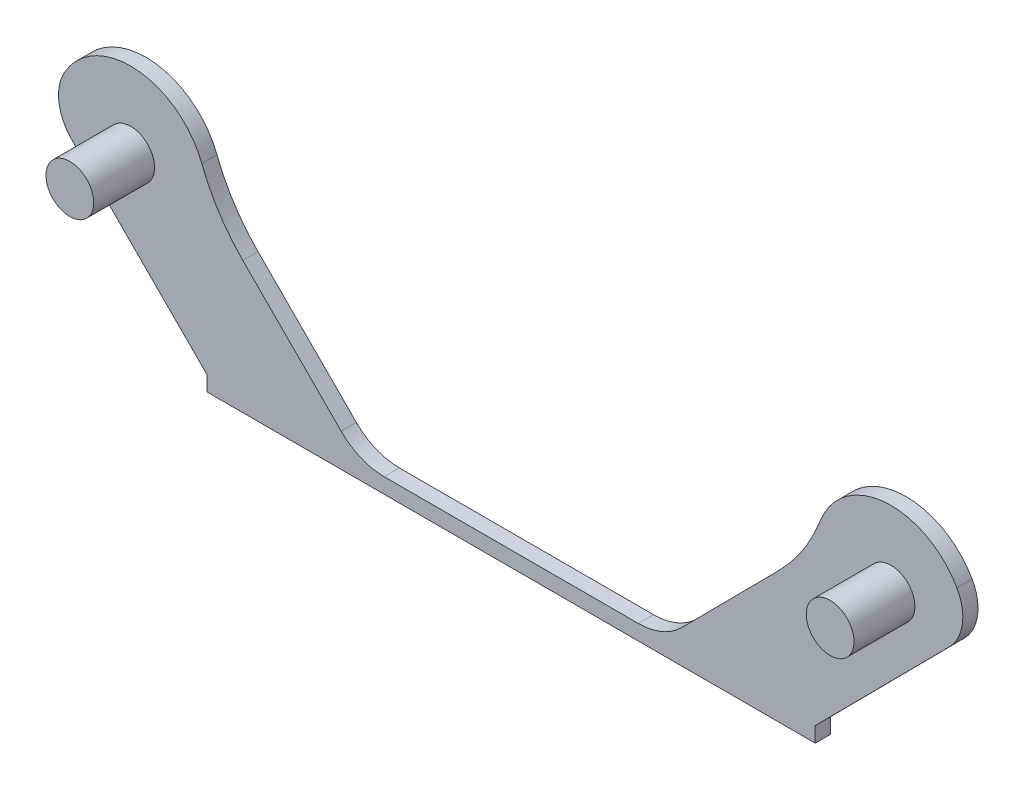
SolidWorks part; units mm, degrees
material "1060 Alloy"
ref_plane "Front Plane" through (0, 0, 0) normal (0, 0, 1) x (1, 0, 0)
ref_plane "Top Plane" through (0, 0, 0) normal (0, 1, 0) x (1, 0, 0)
ref_plane "Right Plane" through (0, 0, 0) normal (1, 0, 0) x (0, 0, -1)
sketch "Sketch1" plane through (0, 0, 0) normal (0, 0, 1) x (1, 0, 0)
  line L5 (50.8, 0) -> (-50.8, 0)
  line L6 (-50.8, 2.54) -> (-50.8, 0)
  line L8 (-50.8, 2.54) -> (-73.3412, 25.1777)
  line L16 (50.8, 2.54) -> (50.8, 0)
  line L17 (-44.7815, 22.0182) -> (-28.3648, 5.5312)
  line L19 (44.8202, 22.0295) -> (28.4837, 5.5477)
  line L20 (21.2678, 2.54) -> (-21.1652, 2.54)
  line L21 (73.2365, 25.1762) -> (50.8, 2.54)
  arc A0 (-74.5846, 34.2871) -> (-51.6423, 32.612) centre (-63.5068, 28.0625) cw
  arc A1 (74.4553, 34.2951) -> (51.6365, 32.586) centre (63.4487, 28.0625) ccw
  circle A2 centre (-63.5068, 28.0625) radius 3.9878
  circle A3 centre (63.4487, 28.0625) radius 3.9878
  arc A4 (-73.3412, 25.1777) -> (-74.5846, 34.2871) centre (-67.9415, 30.5544) cw
  arc A5 (44.8202, 22.0295) -> (51.6365, 32.586) centre (23.1723, 43.4864) ccw
  arc A6 (-44.7815, 22.0182) -> (-51.6423, 32.612) centre (-23.1829, 43.5247) cw
  arc A7 (74.4553, 34.2951) -> (73.2365, 25.1762) centre (67.8246, 30.5404) cw
  arc A8 (21.2678, 2.54) -> (28.4837, 5.5477) centre (21.2678, 12.7) ccw
  arc A9 (-21.1652, 2.54) -> (-28.3648, 5.5312) centre (-21.1652, 12.7) cw
  point P0 (0, 0)
  point P16 (-76.2136, 28.0625)
  point P18 (0, 0)
  point P26 (76.0974, 28.0625)
  point P29 (25.5026, 2.54)
  point P32 (-25.3864, 2.54)
  dimension "D3" = 2.54
  dimension "D4" = 7.9756
  dimension "D5" = 7.9756
  dimension "D6" = 12.7068
  dimension "D7" = 12.6487
  dimension "D14" = 7.62
  dimension "D15" = 30.48
  dimension "D16" = 30.48
  dimension "D17" = 7.62
  dimension "D21" = 10.16
  dimension "D22" = 10.16
  dimension "D1" = 101.6
  dimension "D2" = 2.54
  dimension "D8" = 50.8889
  dimension "D9" = 63.4487
  dimension "D10" = 25.5026
  dimension "D11" = 63.5068
  dimension "D12" = 28.0625
  dimension "D13" = 28.0625
  dimension "D18" = 23.1723
  dimension "D19" = 44.8202
  dimension "D20" = 23.1829
extrude "Boss-Extrude1" add sketch "Sketch1" along normal blind 2.54
extrude "Boss-Extrude2" add sketch "Sketch1<4>" along normal blind 12.7 separate body contours A2
sketch "Sketch1<4>" plane through (0, 0, 0) normal (0, 0, 1) x (1, 0, 0) same geometry as "Sketch1"
extrude "Boss-Extrude3" add sketch "Sketch1<5>" along normal blind 12.7 separate body contours A3
sketch "Sketch1<5>" plane through (0, 0, 0) normal (0, 0, 1) x (1, 0, 0) same geometry as "Sketch1"
